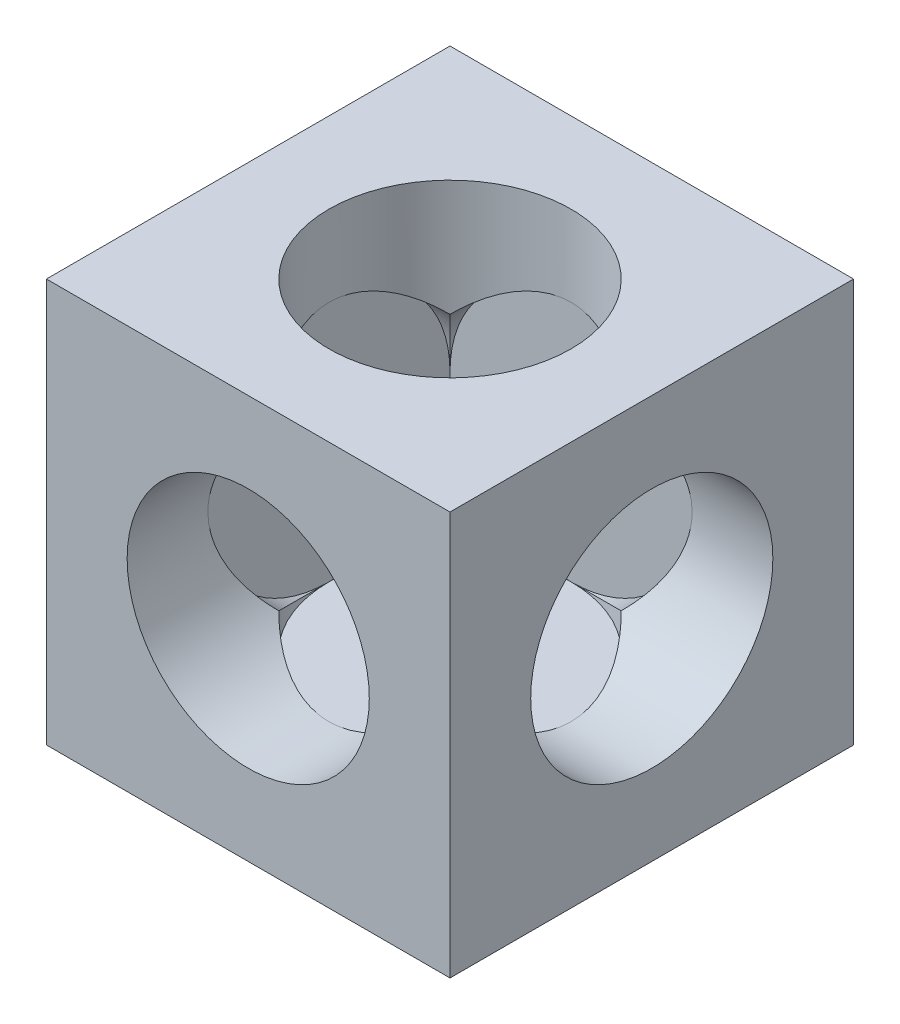
SolidWorks part; units mm, degrees
material "Acciaio in lega fuso"
ref_plane "Piano frontale" through (0, 0, 0) normal (0, 0, 1) x (1, 0, 0)
ref_plane "Piano superiore" through (0, 0, 0) normal (0, 1, 0) x (1, 0, 0)
ref_plane "Piano destro" through (0, 0, 0) normal (1, 0, 0) x (0, 0, -1)
sketch "Schizzo1" plane through (0, 0, 0) normal (0, 0, 1) x (1, 0, 0)
  line L1 (5, -5) -> (-5, -5)
  line L2 (5, -5) -> (5, 5)
  line L3 (5, 5) -> (-5, 5)
  line L4 (-5, -5) -> (-5, 5)
  line L5 (5, -5) -> (-5, 5) construction
  line L6 (5, 5) -> (-5, -5) construction
  point P0 (0, 0)
  dimension "D1" = 10
extrude "Estrusione-Estrusione1" add sketch "Schizzo1" along normal blind 10
hole_wizard "Foro filettato M3x0.5-1" positions "Schizzo3" profile "Schizzo2" tap size "M3x0.5" standard "Ansi Metric" end condition through all
sketch "Schizzo3" plane through (0, 0, 10) normal (0, 0, 1) x (1, 0, 0)
  point P0 (0, 0)
sketch "Schizzo2" plane through (0, 0, 10) normal (1, 0, 0) x (0, -1, 0)
  line L0 (0, 0) -> (0, 10)
  line L1 (0, 10) -> (1.25, 10)
  line L2 (1.25, 10) -> (1.25, 0)
  line L5 (1.25, 0) -> (0, 0)
  line L11 (0, -6.35) -> (0, 107.95) construction
  dimension "Thread Major Dia." = 2.5
  dimension "Thru Tap Drill Depth" = 10
hole_wizard "Foro filettato M3x0.5-2" positions "Schizzo5" profile "Schizzo4" tap size "M3x0.5" standard "Ansi Metric" end condition through all
sketch "Schizzo5" plane through (5, 0, 0) normal (1, 0, 0) x (0, 0, -1)
  point P0 (-5, 0)
sketch "Schizzo4" plane through (5, 0, 5) normal (0, 1, 0) x (0, 0, -1)
  line L0 (0, 0) -> (0, 10)
  line L1 (0, 10) -> (1.25, 10)
  line L2 (1.25, 10) -> (1.25, 0)
  line L5 (1.25, 0) -> (0, 0)
  line L11 (0, -6.35) -> (0, 107.95) construction
  dimension "Thread Major Dia." = 2.5
  dimension "Thru Tap Drill Depth" = 10
hole_wizard "Foro filettato M3x0.5-3" positions "Schizzo7" profile "Schizzo6" tap size "M3x0.5" standard "Ansi Metric" end condition through all
sketch "Schizzo7" plane through (0, -5, 0) normal (0, -1, 0) x (-1, 0, 0)
  point P0 (0, -5)
sketch "Schizzo6" plane through (0, -5, 5) normal (1, 0, 0) x (0, 0, -1)
  line L0 (0, 0) -> (0, 10)
  line L1 (0, 10) -> (1.25, 10)
  line L2 (1.25, 10) -> (1.25, 0)
  line L5 (1.25, 0) -> (0, 0)
  line L11 (0, -6.35) -> (0, 107.95) construction
  dimension "Thread Major Dia." = 2.5
  dimension "Thru Tap Drill Depth" = 10
sketch "Schizzo8" plane through (0, 0, 10) normal (0, 0, 1) x (1, 0, 0)
  circle A0 centre (0, 0) radius 3
  dimension "D1" = 6
extrude "Taglio-Estrusione1" cut sketch "Schizzo8" against normal blind 8
sketch "Schizzo9" plane through (5, 0, 0) normal (1, 0, 0) x (0, 0, -1)
  circle A0 centre (-5, 0) radius 3
  dimension "D1" = 6
extrude "Taglio-Estrusione2" cut sketch "Schizzo9" against normal blind 8
sketch "Schizzo10" plane through (0, 5, 0) normal (0, 1, 0) x (1, 0, 0)
  circle A0 centre (0, -5) radius 3
  dimension "D1" = 6
extrude "Taglio-Estrusione3" cut sketch "Schizzo10" against normal blind 8
